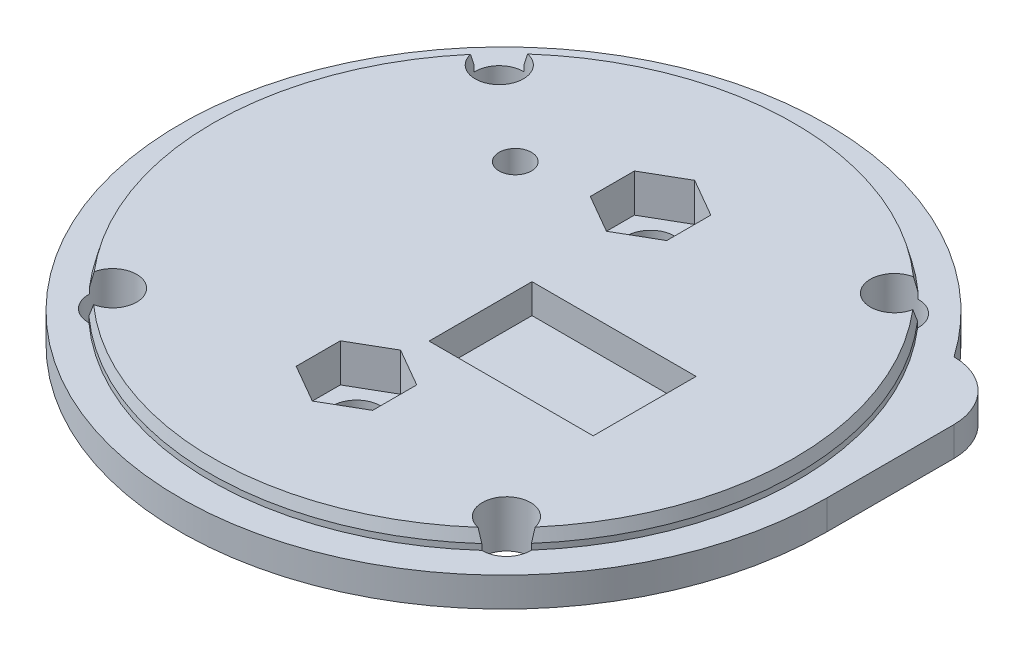
SolidWorks part; units mm, degrees
ref_plane "Спереди" through (0, 0, 0) normal (0, 0, 1) x (1, 0, 0)
ref_plane "Сверху" through (0, 0, 0) normal (0, 1, 0) x (1, 0, 0)
ref_plane "Справа" through (0, 0, 0) normal (1, 0, 0) x (0, 0, -1)
sketch "Эскиз1" plane through (0, 0, 0) normal (0, 1, 0) x (1, 0, 0)
  circle A0 centre (0, 0) radius 55
  dimension "D1" = 110
extrude "Бобышка-Вытянуть1" add sketch "Эскиз1" along normal blind 5
sketch "Эскиз2" plane through (0, 5, 0) normal (0, 1, 0) x (1, 0, 0)
  circle A0 centre (0, 0) radius 49.9
  dimension "D1" = 99.8
extrude "Бобышка-Вытянуть2" add sketch "Эскиз2" along normal blind 3
sketch "Эскиз3" plane through (0, 0, 0) normal (0, -1, 0) x (1, 0, 0)
  line L1 (17.5, -15) -> (-17.5, -15)
  line L2 (17.5, -15) -> (17.5, 15)
  line L3 (17.5, 15) -> (-17.5, 15)
  line L4 (-17.5, -15) -> (-17.5, 15)
  line L5 (17.5, -15) -> (-17.5, 15) construction
  line L6 (17.5, 15) -> (-17.5, -15) construction
  point P0 (0, 0)
  dimension "D1" = 35
  dimension "D2" = 30
extrude "Бобышка-Вытянуть3" add sketch "Эскиз3" along normal blind 25
sketch "Эскиз5" plane through (0, 0, 0) normal (0, -1, 0) x (1, 0, 0)
  line L0 (23.35, -22.85) -> (39.3102, -38.467) construction
  line L5 (-23.35, 22.85) -> (23.35, -22.85) construction
  line L6 (-23.35, -22.85) -> (23.35, 22.85) construction
  line L7 (-23.35, 22.85) -> (-39.3095, 38.4677) construction
  line L8 (23.35, 22.85) -> (39.1401, 38.6401) construction
  line L9 (-23.35, -22.85) -> (-39.3095, -38.4677) construction
  circle A0 centre (0, 0) radius 55 construction
  circle A1 centre (33.5922, -32.8719) radius 4.1
  circle A2 centre (-33.5917, -32.8724) radius 4.1
  circle A3 centre (-33.5917, 32.8724) radius 4.1
  circle A4 centre (33.4832, 32.9832) radius 4.1
  point P0 (0, 0)
  dimension "D3" = 8.2
  dimension "D1" = 46.7
  dimension "D2" = 45.7
  dimension "D4" = 8
  dimension "D5" = 8
  dimension "D6" = 8
  dimension "D7" = 8
extrude "Вырез-Вытянуть2" cut sketch "Эскиз5" against normal through all
sketch "Эскиз6" plane through (0, 8, 0) normal (0, 1, 0) x (1, 0, 0)
  line L0 (0, 0) -> (0.0004, 49.9) construction
  line L1 (0.0001, 20) -> (-17.9999, 20) construction
  arc A0 (33.5133, 36.9712) -> (-33.5128, 36.9717) centre (0, 0) ccw construction
  circle A1 centre (-17.9999, 20) radius 2.75
  dimension "D3" = 5.5
  dimension "D1" = 20
  dimension "D2" = 18
extrude "Вырез-Вытянуть3" cut sketch "Эскиз6" against normal through all
sketch "Sketch1" plane through (0, 0, 0) normal (0, -1, 0) x (1, 0, 0)
  line L0 (55, 0) -> (55, -31.5467)
  line L1 (0, 0) -> (55, 0) construction
  line L2 (12.0631, 36.7669) -> (11.7652, 37.2607) construction
  line L3 (55, -31.5467) -> (45.0534, -31.5467)
  line L6 (0, 0) -> (0, -55) construction
  line L7 (0, 0) -> (45.0534, -31.5467) construction
  circle A0 centre (0, 0) radius 55 construction
  arc A1 (45.0534, -31.5467) -> (55, 0) centre (0, 0) ccw
  dimension "D1" = 90
  dimension "D2" = 55
extrude "Boss-Extrude1" add sketch "Sketch1" against normal up to surface (5 mm away) up to face at (-0.025, 5, 0.0254)
fillet "Fillet1" radius 10 1 edges at (55, 2.5, -31.5467)
sketch "Sketch2" plane through (-17.5, 0, 0) normal (-1, 0, 0) x (0, 0, 1)
  line L0 (-15, -25) -> (15, 0) construction
  line L2 (10.125, -17.675) -> (-10.125, -17.675)
  line L3 (10.125, -17.675) -> (10.125, -7.325)
  line L4 (10.125, -7.325) -> (-10.125, -7.325)
  line L5 (-10.125, -17.675) -> (-10.125, -7.325)
  line L6 (10.125, -17.675) -> (-10.125, -7.325) construction
  line L7 (10.125, -7.325) -> (-10.125, -17.675) construction
  point P2 (0, -12.5)
  point P10 (0, -12.5)
  dimension "D1" = 20.25
  dimension "D2" = 10.35
extrude "Cut-Extrude1" cut sketch "Sketch2" against normal through all
sketch "Sketch3" plane through (0, 8, 0) normal (0, 1, 0) x (1, 0, 0)
  line L0 (49.6489, -5) -> (-49.6489, -5) construction
  line L2 (1.0921, 3.75) -> (28.9921, 3.75)
  line L3 (1.0921, 3.75) -> (1.0921, -13.75)
  line L4 (1.0921, -13.75) -> (28.9921, -13.75)
  line L5 (28.9921, 3.75) -> (28.9921, -13.75)
  line L6 (1.0921, 3.75) -> (28.9921, -13.75) construction
  line L7 (1.0921, -13.75) -> (28.9921, 3.75) construction
  arc A0 (37.5803, -32.8288) -> (37.6888, 32.7042) centre (0, 0) ccw construction
  arc A1 (-37.6883, 32.7048) -> (-37.6883, -32.7048) centre (0, 0) ccw construction
  point P8 (15.0421, -5)
  point P18 (0, -5)
  dimension "D1" = 27.9
  dimension "D2" = 17.5
  dimension "D3" = 5
extrude "Cut-Extrude2" cut sketch "Sketch3" against normal blind 5
chamfer "Chamfer1" distance 2 angle 15 4 edges at (49.8999, 8, 0.0826) (-49.9, 8, 0) (0.0004, 8, -49.9) (-0.0824, 8, 49.8999) first distance on face at (43.7672, 6.5, 0.0724) first distance on face at (-43.7941, 6.5, 0) first distance on face at (0.0003, 6.5, -43.4357) first distance on face at (-0.0718, 6.5, 43.4634)
sketch "Sketch4" plane through (0, -25, 0) normal (0, -1, 0) x (1, 0, 0)
  line L0 (-17.5, 0) -> (17.5, 0) construction
  line L1 (-17.5, 15) -> (-17.5, -15) construction
  line L2 (17.5, -15) -> (17.5, 15) construction
  line L4 (17.5, -15) -> (-17.5, -15)
  line L5 (17.5, -15) -> (17.5, 15)
  line L6 (17.5, 15) -> (-17.5, 15)
  line L7 (-17.5, -15) -> (-17.5, 15)
  line L8 (17.5, -15) -> (-17.5, 15) construction
  line L9 (17.5, 15) -> (-17.5, -15) construction
  point P6 (0, 0)
extrude "Cut-Extrude3" cut sketch "Sketch4" against normal blind 12.5
sketch "Sketch5" plane through (0, -7.325, 0) normal (0, -1, 0) x (1, 0, 0)
  line L0 (0, 10.125) -> (0, -10.125) construction
  line L1 (17.5, 10.125) -> (-17.5, 10.125) construction
  line L2 (17.5, -10.125) -> (-17.5, -10.125) construction
  line L4 (10, -35) -> (-10, -35)
  line L5 (10, -35) -> (10, 35)
  line L6 (10, 35) -> (-10, 35)
  line L7 (-10, -35) -> (-10, 35)
  line L8 (10, -35) -> (-10, 35) construction
  line L9 (10, 35) -> (-10, -35) construction
  point P6 (0, 0)
  dimension "D1" = 20
  dimension "D2" = 70
extrude "Boss-Extrude2" add sketch "Sketch5" against normal up to surface (7.325 mm away) from offset 2 up to face at (-17.9999, 0, -17.25) offset against normal yes
sketch "Sketch6" plane through (0, -5.325, 0) normal (0, -1, 0) x (1, 0, 0)
  line L0 (10, 25) -> (-10, 25) construction
  line L1 (10, 15) -> (10, 35) construction
  line L2 (-10, 35) -> (-10, 15) construction
  line L3 (10, -25) -> (-10, -25) construction
  line L4 (10, -35) -> (10, -15) construction
  line L5 (-10, -15) -> (-10, -35) construction
  circle A0 centre (0, 25) radius 4.1
  circle A1 centre (0, -25) radius 4.1
  dimension "D3" = 8.2
  dimension "D1" = 10
  dimension "D2" = 10
  dimension "D4" = 25
extrude "Cut-Extrude4" cut sketch "Sketch6" against normal through all
sketch "Sketch7" plane through (0, 8, 0) normal (0, 1, 0) x (1, 0, 0)
  line L1 (0, -32.5) -> (6.4952, -28.75)
  line L2 (6.4952, -28.75) -> (6.4952, -21.25)
  line L3 (6.4952, -21.25) -> (0, -17.5)
  line L4 (0, -17.5) -> (-6.4952, -21.25)
  line L5 (-6.4952, -21.25) -> (-6.4952, -28.75)
  line L6 (-6.4952, -28.75) -> (0, -32.5)
  line L7 (0, 17.5) -> (6.4952, 21.25)
  line L8 (6.4952, 21.25) -> (6.4952, 28.75)
  line L9 (6.4952, 28.75) -> (0, 32.5)
  line L10 (0, 32.5) -> (-6.4952, 28.75)
  line L11 (-6.4952, 28.75) -> (-6.4952, 21.25)
  line L12 (-6.4952, 21.25) -> (0, 17.5)
  circle A0 centre (0, -25) radius 7.5 construction
  circle A1 centre (0, 25) radius 7.5 construction
  dimension "D1" = 15
extrude "Cut-Extrude5" cut sketch "Sketch7" against normal blind 6.5
